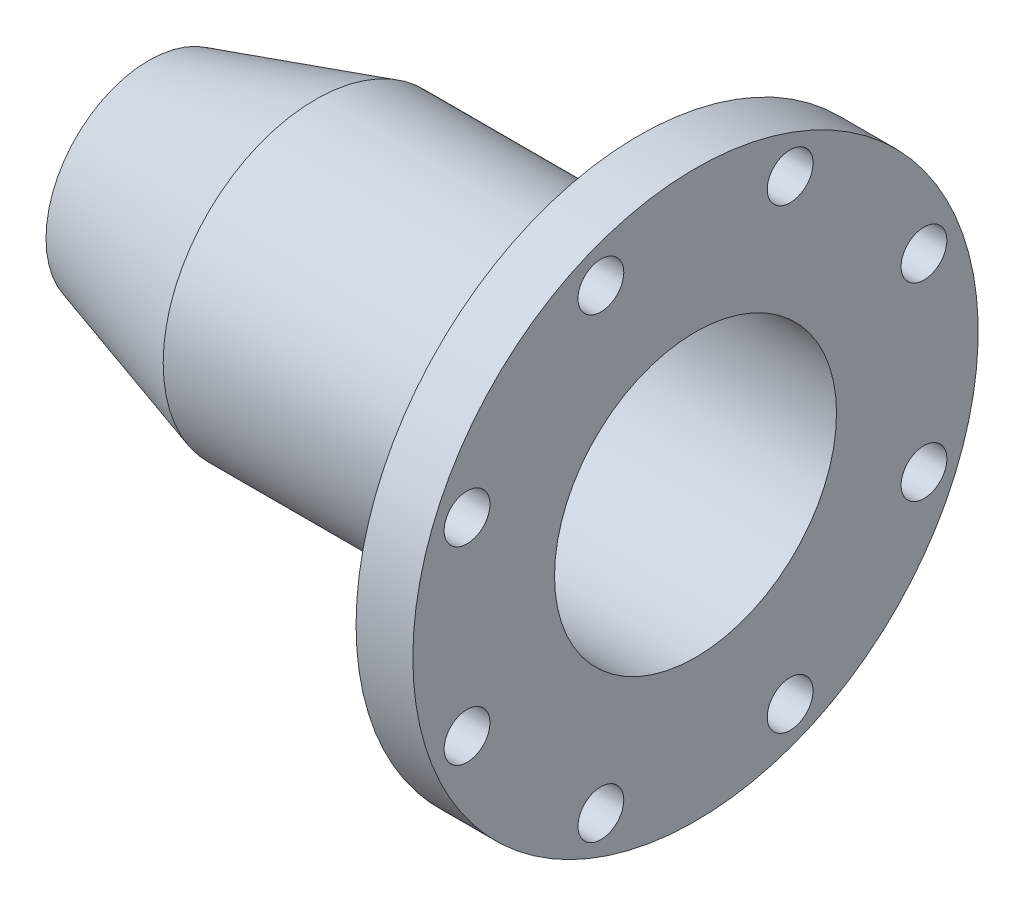
SolidWorks part; units mm, degrees
other "Camera1"
material "PP Homopolymer"
ref_plane "Front Plane" through (0, 0, 0) normal (0, 0, 1) x (1, 0, 0)
ref_plane "Top Plane" through (0, 0, 0) normal (0, 1, 0) x (1, 0, 0)
ref_plane "Right Plane" through (0, 0, 0) normal (1, 0, 0) x (0, 0, -1)
sketch "Sketch1" plane through (0, 0, 0) normal (0, 0, 1) x (1, 0, 0)
  line L0 (0, 0) -> (541.4119, 0) construction
  line L1 (266.7, 68.795) -> (266.7, 137.92)
  line L2 (266.7, 137.92) -> (239.01, 137.92)
  line L3 (239.01, 137.92) -> (239.01, 74.295)
  line L4 (239.01, 74.295) -> (81.28, 74.295)
  line L5 (239.01, 68.795) -> (82.0785, 68.795)
  line L6 (239.01, 68.795) -> (266.7, 68.795)
  line L7 (81.28, 74.295) -> (0, 50.1868)
  line L8 (82.0785, 68.795) -> (0, 44.45)
  line L9 (0, 50.1868) -> (0, 44.45)
  line L10 (239.01, 74.295) -> (266.7, 74.295)
  dimension "D2" = 27.69
  dimension "D3" = 74.295
  dimension "D4" = 185.42
  dimension "D5" = 266.7
  dimension "D6" = 5.5
  dimension "D7" = 5.5
  dimension "D1" = 44.45
revolve "Revolve1" add sketch "Sketch1" angle 360 about L0 region at (252.855, 71.4786, 0) region at (252.855, 106.1075, 0)
sketch "Sketch3" plane through (266.7, 0, 0) normal (1, 0, 0) x (0, 0, -1)
  line L0 (0, 0) -> (0, 120.65) construction
  line L1 (0, 0) -> (-46.1708, 111.4661) construction
  circle A0 centre (0, 0) radius 120.65 construction
  dimension "D1" = 241.3
  dimension "D2" = 22.5
hole_wizard "1/16 (0.88) Diameter Hole1" positions "3DSketch2" profile "Sketch7" hole size "1/16" standard "ANSI Inch" end condition through all
sketch3d "3DSketch2"
  point P0 (266.7, 111.4661, 46.1708)
sketch "Sketch7" plane through (266.7, 111.4661, 46.1708) normal (0, 1, 0) x (0, 0, -1)
  line L0 (0, 0) -> (0, 266.7)
  line L1 (0, 266.7) -> (11.176, 266.7)
  line L2 (11.176, 266.7) -> (11.176, 0)
  line L5 (11.176, 0) -> (0, 0)
  line L11 (0, -6.35) -> (0, 107.95) construction
  dimension "Thru Hole Dia." = 22.352
  dimension "Thru Hole Depth" = 266.7
pattern_circular "CirPattern1" count 8 over 360 about axis through (0, 0, 0) along (-1, 0, 0) of "1/16 (0.88) Diameter Hole1"
equation "\"Wall Thickness\"= 5.5"
equation "\"D6@Sketch1\"=\"Wall Thickness\""
equation "\"Nozzle diameter\"= 3.5 * 25.4"
equation "\"D7@Sketch1\"=\"Wall Thickness\""
equation "\"D1@Sketch1\"=\"Nozzle diameter\"/2"
